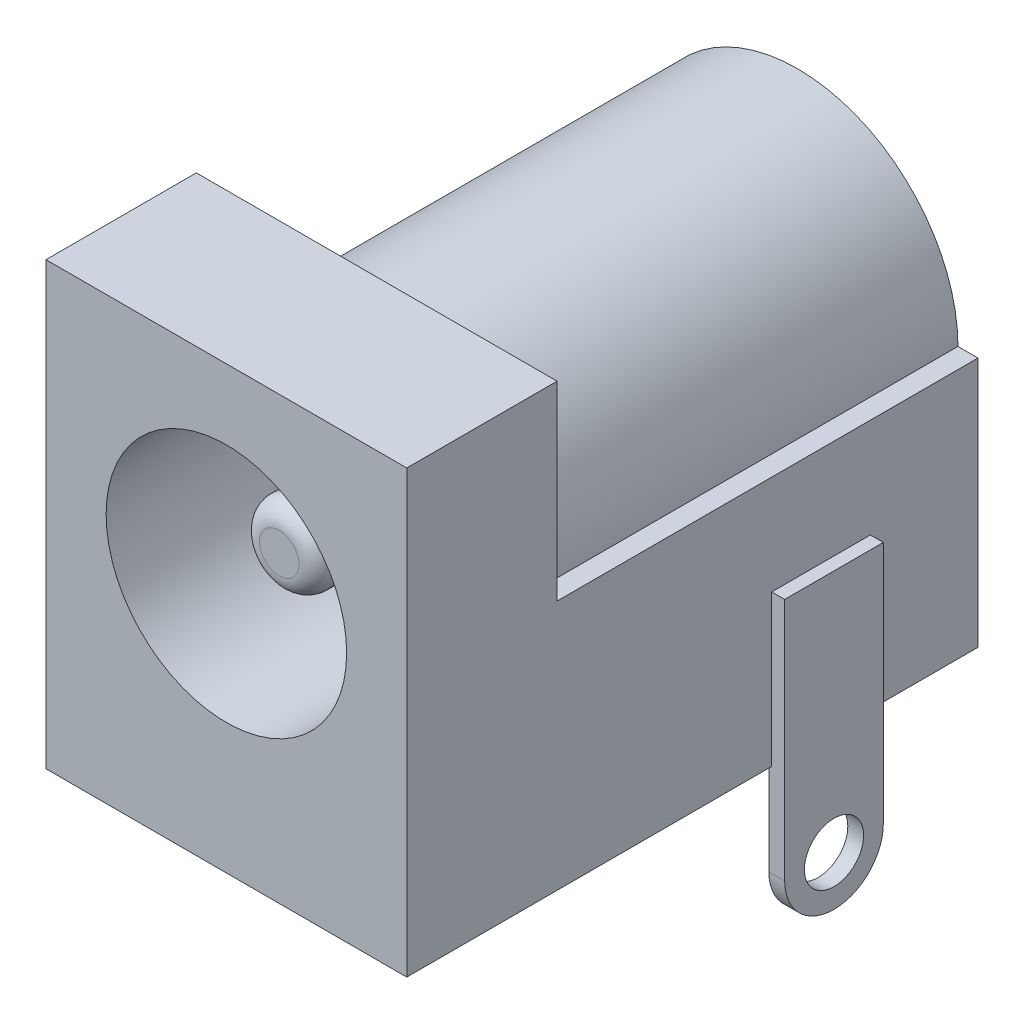
SolidWorks part; units mm, degrees
ref_plane "Plane1" through (0, 0, 0) normal (0, 0, 1) x (1, 0, 0)
ref_plane "Plane2" through (0, 0, 0) normal (0, 1, 0) x (1, 0, 0)
ref_plane "Plane3" through (0, 0, 0) normal (1, 0, 0) x (0, 0, -1)
sketch "Sketch1" plane through (0, 0, 0) normal (0, 0, 1) x (1, 0, 0)
  line L1 (-4.572, 0) -> (4.572, 0)
  line L2 (-4.572, 0) -> (-4.572, 11.176)
  line L3 (-4.572, 11.176) -> (4.572, 11.176)
  line L4 (4.572, 0) -> (4.572, 11.176)
  dimension "D1" = 9.144
  dimension "D2" = 11.176
extrude "Base-Extrude" add sketch "Sketch1" against normal blind 3.81
sketch "Sketch2" plane through (0, 0, -3.81) normal (0, 0, -1) x (-1, 0, 0)
  line L0 (4.572, 0) -> (-4.572, 0) construction
  line L1 (-4.572, 0) -> (-4.572, 11.176) construction
  line L2 (4.572, 11.176) -> (4.572, 0) construction
  line L3 (-4.572, 0) -> (-4.572, 6.35)
  line L4 (4.572, 0) -> (-4.572, 0)
  line L5 (4.572, 6.35) -> (4.572, 0)
  line L6 (-4.064, 6.35) -> (-4.572, 6.35)
  line L7 (4.064, 6.35) -> (4.572, 6.35)
  arc A0 (-4.064, 6.35) -> (4.064, 6.35) centre (0, 6.35) cw
  dimension "D1" = 4.064
  dimension "D2" = 6.35
extrude "Boss-Extrude1" add sketch "Sketch2" along normal blind 10.668
sketch "Sketch3" plane through (0, 0, 0) normal (0, 0, 1) x (1, 0, 0)
  circle A0 centre (0, 6.35) radius 3.048
  dimension "D1" = 6.096
extrude "Cut-Extrude1" cut sketch "Sketch3" against normal blind 9.144
sketch "Sketch4" plane through (0, 0, -9.144) normal (0, 0, 1) x (1, 0, 0)
  circle A0 centre (0, 6.35) radius 1
  dimension "D1" = 2
extrude "Extrude1" add sketch "Sketch4" along normal offset from surface (7.804 mm away) 1.34 up to face at (3.048, 6.35, 0)
fillet "Fillet1" radius 0.5 1 edges at (-1, 6.35, -1.34)
ref_plane "Plane4" through (4.7, 0, 0) normal (1, 0, 0) x (0, 0, -1)
sketch "Sketch5" plane through (4.7, 0, 0) normal (1, 0, 0) x (0, 0, -1)
  line L0 (11.75, 3.83) -> (11.75, -2.35)
  line L1 (9.25, 3.83) -> (9.25, -2.35)
  line L2 (9.25, 3.83) -> (11.75, 3.83)
  line L3 (14.478, 0) -> (0, 0) construction
  line L4 (0, 0) -> (0, 11.176) construction
  line L6 (14.478, 6.35) -> (3.81, 6.35) construction
  arc A0 (11.75, -2.35) -> (9.25, -2.35) centre (10.5, -2.35) cw
  circle A1 centre (10.5, -2.35) radius 0.75
  dimension "D2" = 3.6
  dimension "D5" = 1.5
  dimension "D1" = 2.5
  dimension "D3" = 10.5
  dimension "D4" = 2.52
extrude "Extrude2" add sketch "Sketch5" along normal mid plane 0.4
ref_plane "Plane5" through (0, 0, -7.5) normal (0, 0, 1) x (-1, 0, 0)
sketch "Sketch6" plane through (0, 0, -7.5) normal (0, 0, 1) x (-1, 0, 0)
  line L0 (0, 0) -> (0, 5.5847) construction
  line L1 (-1.1, 0) -> (-1.1, 2.5)
  line L2 (4.572, 0) -> (-4.572, 0) construction
  line L3 (1.1, 0) -> (1.1, 2.5)
  line L4 (1.1, 0) -> (-1.1, 0)
  arc A0 (1.1, 2.5) -> (-1.1, 2.5) centre (0, 2.5) ccw
  circle A1 centre (0, 2.5) radius 0.75
  dimension "D2" = 3.6
  dimension "D3" = 1.5
  dimension "D1" = 2.2
extrude "Extrude3" add sketch "Sketch6" along normal mid plane 0.3
ref_plane "Plane6" through (0, 0, -13.7) normal (0, 0, 1) x (1, 0, 0)
sketch "Sketch7" plane through (0, 0, -13.7) normal (0, 0, 1) x (1, 0, 0)
  line L0 (0, 0) -> (0, -4.6387) construction
  line L1 (1.425, 0) -> (1.425, -2.175)
  line L2 (4.572, 0) -> (-4.572, 0) construction
  line L3 (-1.425, 0) -> (-1.425, -2.175)
  line L4 (1.425, 0) -> (-1.425, 0)
  arc A0 (1.425, -2.175) -> (-1.425, -2.175) centre (0, -2.175) cw
  circle A3 centre (0, -2.175) radius 0.75
  dimension "D2" = 3.6
  dimension "D3" = 1.5
  dimension "D1" = 2.85
extrude "Extrude4" add sketch "Sketch7" along normal mid plane 0.4
